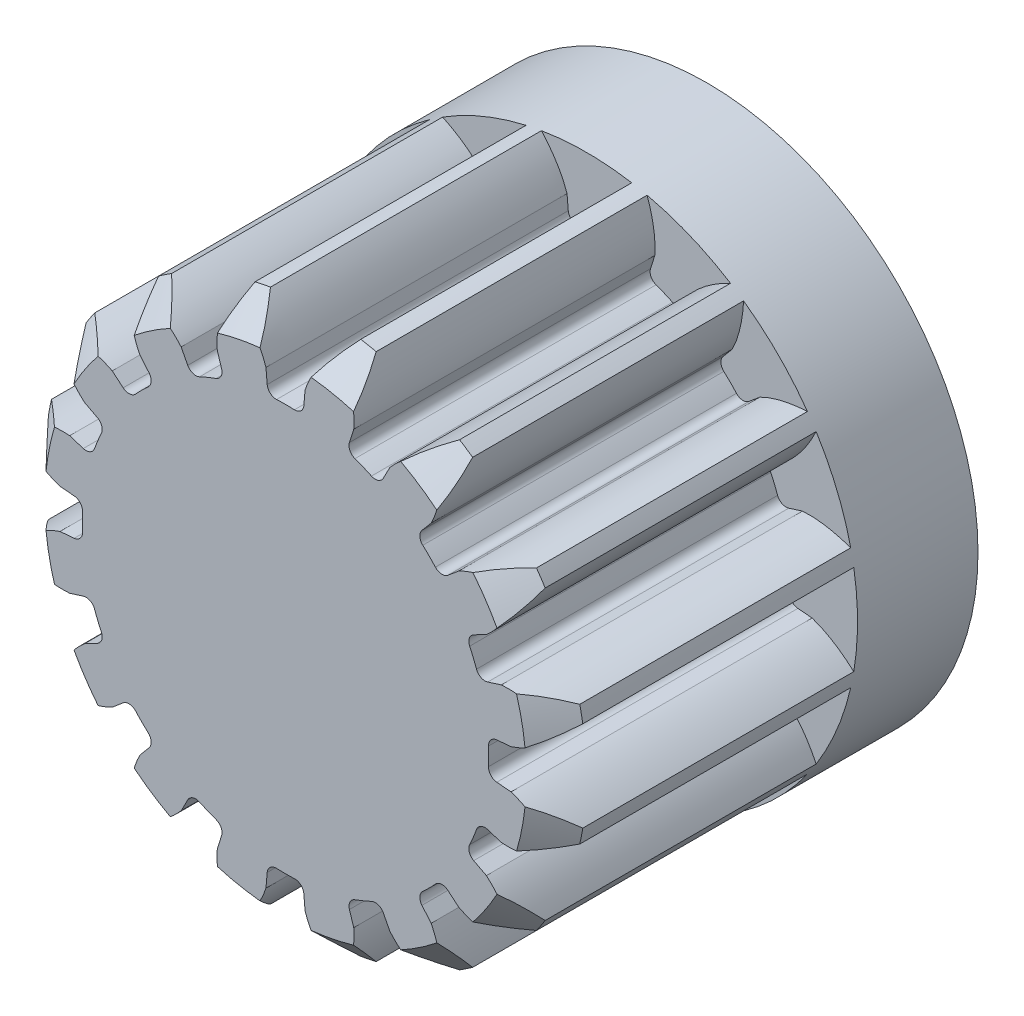
SolidWorks part; units mm, degrees
ref_plane "前视基准面" through (0, 0, 0) normal (0, 0, 1) x (1, 0, 0)
ref_plane "上视基准面" through (0, 0, 0) normal (0, 1, 0) x (1, 0, 0)
ref_plane "右视基准面" through (0, 0, 0) normal (1, 0, 0) x (0, 0, -1)
sketch "直齿轮" plane through (0, 0, 0) normal (0, 0, 1) x (1, 0, 0)
  line L0 (0, 9) -> (0, -9) construction
  line L1 (0, 0) -> (-0.6495, 7.4894)
  line L2 (0, 0) -> (0.6495, 7.4894)
  circle A0 centre (0, 0) radius 9
  arc A1 (0.7841, 7.9615) -> (-0.7841, 7.9615) centre (0, 0) ccw
  circle A2 centre (0, 0) radius 6.75
  circle A3 centre (0, 0) radius 7.5175
  spline S0 degree 4 poles (0.0781, 7.329) (0.077, 7.3576) (0.0721, 7.4145) (0.0444, 7.5728) (-0.044, 7.8662) (-0.2393, 8.2942) (-0.5932, 8.8351) (-1.1432, 9.4579) (-1.8896, 10.0833) (-2.7997, 10.6455) (-3.8544, 11.1099) (-4.9579, 11.4403) (-6.0912, 11.644) (-7.296, 11.7321) (-8.7914, 11.6852) (-10.5554, 11.401) (-12.5357, 10.7749) (-14.6014, 9.7479) (-16.4971, 8.4351) (-18.1977, 6.8792) (-19.6854, 5.1194) (-20.7905, 3.4336) (-21.5928, 1.9052) (-22.1636, 0.5865) (-22.5615, -0.4928) (-22.9004, -1.5905) (-23.1806, -2.7072) (-23.4023, -3.8323) (-23.5456, -4.8331) (-23.6323, -5.6826) (-23.6776, -6.3617) (-23.699, -6.8068) (-23.7118, -7.3077) (-23.715, -7.634) (-23.7125, -8.1596) (-23.6992, -8.5689) (-23.6779, -9.0652) (-23.6471, -9.5073) (-23.6078, -9.983) (-23.5595, -10.4339) (-23.517, -10.787) (-23.4856, -11.012) (-23.4693, -11.1287) knots 0 0 0 0 0 0.002802 0.005604 0.015718 0.02996 0.048734 0.068727 0.096889 0.125051 0.153212 0.181374 0.209535 0.237696 0.271429 0.327752 0.384075 0.440398 0.496721 0.553044 0.609367 0.66569 0.693852 0.722013 0.750174 0.778336 0.806497 0.834659 0.86282 0.876901 0.890982 0.900036 0.909091 0.920455 0.931818 0.943182 0.954545 0.965909 0.977273 0.988636 1 1 1 1 1 construction
  spline S1 degree 4 poles (-0.6495, 7.4894) (-0.6695, 7.5517) (-0.7404, 7.7468) (-0.9116, 8.1035) (-1.2415, 8.6) (-1.7832, 9.2048) (-2.5168, 9.8107) (-3.41, 10.3537) (-4.4437, 10.8002) (-5.5242, 11.1155) (-6.6329, 11.3066) (-7.8108, 11.3844) (-9.2716, 11.3283) (-10.9933, 11.0384) (-12.9239, 10.4129) (-14.9352, 9.3952) (-16.7784, 8.0994) (-18.4293, 6.5673) (-19.8708, 4.8376) (-20.9389, 3.1827) (-21.7123, 1.6839) (-22.2609, 0.3914) (-22.6422, -0.6659) (-22.9658, -1.7408) (-23.2319, -2.8339) (-23.4407, -3.9348) (-23.5738, -4.9136) (-23.6527, -5.7442) (-23.6922, -6.408) (-23.7101, -6.8431) (-23.7191, -7.3326) (-23.72, -7.6515) (-23.7154, -8.0397) (-23.7087, -8.2696) (-23.7044, -8.3867) (-23.7041, -8.3947) knots 0.009155 0.009155 0.009155 0.009155 0.009155 0.015718 0.02996 0.048734 0.068727 0.096889 0.125051 0.153212 0.181374 0.209535 0.237696 0.271429 0.327752 0.384075 0.440398 0.496721 0.553044 0.609367 0.66569 0.693852 0.722013 0.750174 0.778336 0.806497 0.834659 0.86282 0.876901 0.890982 0.900036 0.909091 0.920455 0.931818 0.932653 0.932653 0.932653 0.932653 0.932653
  spline S2 degree 4 poles (-0.0781, 7.329) (-0.077, 7.3576) (-0.0721, 7.4145) (-0.0444, 7.5728) (0.044, 7.8662) (0.2393, 8.2942) (0.5932, 8.8351) (1.1432, 9.4579) (1.8896, 10.0833) (2.7997, 10.6455) (3.8544, 11.1099) (4.9579, 11.4403) (6.0912, 11.644) (7.296, 11.7321) (8.7914, 11.6852) (10.5554, 11.401) (12.5357, 10.7749) (14.6014, 9.7479) (16.4971, 8.4351) (18.1977, 6.8792) (19.6854, 5.1194) (20.7905, 3.4336) (21.5928, 1.9052) (22.1636, 0.5865) (22.5615, -0.4928) (22.9004, -1.5905) (23.1806, -2.7072) (23.4023, -3.8323) (23.5456, -4.8331) (23.6323, -5.6826) (23.6776, -6.3617) (23.699, -6.8068) (23.7118, -7.3077) (23.715, -7.634) (23.7125, -8.1596) (23.6992, -8.5689) (23.6779, -9.0652) (23.6471, -9.5073) (23.6078, -9.983) (23.5595, -10.4339) (23.517, -10.787) (23.4856, -11.012) (23.4693, -11.1287) knots 0 0 0 0 0 0.002802 0.005604 0.015718 0.02996 0.048734 0.068727 0.096889 0.125051 0.153212 0.181374 0.209535 0.237696 0.271429 0.327752 0.384075 0.440398 0.496721 0.553044 0.609367 0.66569 0.693852 0.722013 0.750174 0.778336 0.806497 0.834659 0.86282 0.876901 0.890982 0.900036 0.909091 0.920455 0.931818 0.943182 0.954545 0.965909 0.977273 0.988636 1 1 1 1 1 construction
  spline S3 degree 4 poles (0.6495, 7.4894) (0.6695, 7.5517) (0.7404, 7.7468) (0.9116, 8.1035) (1.2415, 8.6) (1.7832, 9.2048) (2.5168, 9.8107) (3.41, 10.3537) (4.4437, 10.8002) (5.5242, 11.1155) (6.6329, 11.3066) (7.8108, 11.3844) (9.2716, 11.3283) (10.9933, 11.0384) (12.9239, 10.4129) (14.9352, 9.3952) (16.7784, 8.0994) (18.4293, 6.5673) (19.8708, 4.8376) (20.9389, 3.1827) (21.7123, 1.6839) (22.2609, 0.3914) (22.6422, -0.6659) (22.9658, -1.7408) (23.2319, -2.8339) (23.4407, -3.9348) (23.5738, -4.9136) (23.6527, -5.7442) (23.6922, -6.408) (23.7101, -6.8431) (23.7191, -7.3326) (23.72, -7.6515) (23.7154, -8.0397) (23.7087, -8.2696) (23.7044, -8.3867) (23.7041, -8.3947) knots 0.009155 0.009155 0.009155 0.009155 0.009155 0.015718 0.02996 0.048734 0.068727 0.096889 0.125051 0.153212 0.181374 0.209535 0.237696 0.271429 0.327752 0.384075 0.440398 0.496721 0.553044 0.609367 0.66569 0.693852 0.722013 0.750174 0.778336 0.806497 0.834659 0.86282 0.876901 0.890982 0.900036 0.909091 0.920455 0.931818 0.932653 0.932653 0.932653 0.932653 0.932653
  dimension "齿顶圆" = 18
  dimension "分度圆" = 16
  dimension "齿根圆" = 13.5
  dimension "基圆直径" = 15.0351
  dimension "D1" = 1.5708
extrude "齿轮毛坯" add sketch "直齿轮" along normal mid plane 11 contours A0
chamfer "轮齿倒角" distance 1 angle 45 2 edges at (9, 0, -5.5) (9, 0, 5.5)
sketch "草图2" plane through (0, 0, 0) normal (0, 0, 1) x (1, 0, 0)
  line L0 (0, 0) -> (-0.6495, 7.4894) construction
  line L1 (0, 0) -> (0.6495, 7.4894) construction
  line L2 (0, 0) -> (-0.6495, 7.4894)
  line L3 (0, 0) -> (0.6495, 7.4894)
  circle A0 centre (0, 0) radius 9 construction
  circle A1 centre (0, 0) radius 9
  circle A2 centre (0, 0) radius 6.75 construction
  circle A3 centre (0, 0) radius 6.75
  spline S0 degree 4 poles (-1000.5185, -8.0268) (-22.1181, -4.5363) (-0.6894, 1.4333) (0.6229, 5.7939) (-1.2415, 8.6) (-1.7832, 9.2048) (-2.5168, 9.8107) (-3.41, 10.3537) (-4.4437, 10.8002) (-5.5242, 11.1155) (-6.6329, 11.3066) (-7.8108, 11.3844) (-9.2716, 11.3283) (-10.9933, 11.0384) (-12.9239, 10.4129) (-14.9352, 9.3952) (-16.7784, 8.0994) (-18.4293, 6.5673) (-19.8708, 4.8376) (-20.9389, 3.1827) (-21.7123, 1.6839) (-22.2609, 0.3914) (-22.6422, -0.6659) (-22.9658, -1.7408) (-23.2319, -2.8339) (-23.4407, -3.9348) (-23.5738, -4.9136) (-23.6527, -5.7442) (-23.6922, -6.408) (-23.7101, -6.8431) (-23.7191, -7.3326) (-23.72, -7.6515) (-23.6888, -10.2883) (-23.3833, -8.7061) (-23.0999, -55.7183) (-17.6667, 991.4298) knots -0.26796 -0.26796 -0.26796 -0.26796 -0.26796 0.015718 0.02996 0.048734 0.068727 0.096889 0.125051 0.153212 0.181374 0.209535 0.237696 0.271429 0.327752 0.384075 0.440398 0.496721 0.553044 0.609367 0.66569 0.693852 0.722013 0.750174 0.778336 0.806497 0.834659 0.86282 0.876901 0.890982 0.900036 0.909091 0.920455 0.931818 1.121583 1.121583 1.121583 1.121583 1.121583 only from (-0.6495, 7.4894) to (-23.7041, -8.3947) construction
  spline S1 degree 4 poles (-0.6495, 7.4894) (-0.6695, 7.5517) (-0.7404, 7.7468) (-0.9116, 8.1035) (-1.2415, 8.6) (-1.7832, 9.2048) (-2.5168, 9.8107) (-3.41, 10.3537) (-4.4437, 10.8002) (-5.5242, 11.1155) (-6.6329, 11.3066) (-7.8108, 11.3844) (-9.2716, 11.3283) (-10.9933, 11.0384) (-12.9239, 10.4129) (-14.9352, 9.3952) (-16.7784, 8.0994) (-18.4293, 6.5673) (-19.8708, 4.8376) (-20.9389, 3.1827) (-21.7123, 1.6839) (-22.2609, 0.3914) (-22.6422, -0.6659) (-22.9658, -1.7408) (-23.2319, -2.8339) (-23.4407, -3.9348) (-23.5738, -4.9136) (-23.6527, -5.7442) (-23.6922, -6.408) (-23.7101, -6.8431) (-23.7191, -7.3326) (-23.72, -7.6515) (-23.7154, -8.0397) (-23.7087, -8.2696) (-23.7044, -8.3867) (-23.7041, -8.3947) knots 0.009155 0.009155 0.009155 0.009155 0.009155 0.015718 0.02996 0.048734 0.068727 0.096889 0.125051 0.153212 0.181374 0.209535 0.237696 0.271429 0.327752 0.384075 0.440398 0.496721 0.553044 0.609367 0.66569 0.693852 0.722013 0.750174 0.778336 0.806497 0.834659 0.86282 0.876901 0.890982 0.900036 0.909091 0.920455 0.931818 0.932653 0.932653 0.932653 0.932653 0.932653
  spline S2 degree 4 poles (1000.5185, -8.0268) (22.1181, -4.5363) (0.6894, 1.4333) (-0.6229, 5.7939) (1.2415, 8.6) (1.7832, 9.2048) (2.5168, 9.8107) (3.41, 10.3537) (4.4437, 10.8002) (5.5242, 11.1155) (6.6329, 11.3066) (7.8108, 11.3844) (9.2716, 11.3283) (10.9933, 11.0384) (12.9239, 10.4129) (14.9352, 9.3952) (16.7784, 8.0994) (18.4293, 6.5673) (19.8708, 4.8376) (20.9389, 3.1827) (21.7123, 1.6839) (22.2609, 0.3914) (22.6422, -0.6659) (22.9658, -1.7408) (23.2319, -2.8339) (23.4407, -3.9348) (23.5738, -4.9136) (23.6527, -5.7442) (23.6922, -6.408) (23.7101, -6.8431) (23.7191, -7.3326) (23.72, -7.6515) (23.6888, -10.2883) (23.3833, -8.7061) (23.0999, -55.7183) (17.6667, 991.4298) knots -0.26796 -0.26796 -0.26796 -0.26796 -0.26796 0.015718 0.02996 0.048734 0.068727 0.096889 0.125051 0.153212 0.181374 0.209535 0.237696 0.271429 0.327752 0.384075 0.440398 0.496721 0.553044 0.609367 0.66569 0.693852 0.722013 0.750174 0.778336 0.806497 0.834659 0.86282 0.876901 0.890982 0.900036 0.909091 0.920455 0.931818 1.121583 1.121583 1.121583 1.121583 1.121583 only from (0.6495, 7.4894) to (23.7041, -8.3947) construction
  spline S3 degree 4 poles (0.6495, 7.4894) (0.6695, 7.5517) (0.7404, 7.7468) (0.9116, 8.1035) (1.2415, 8.6) (1.7832, 9.2048) (2.5168, 9.8107) (3.41, 10.3537) (4.4437, 10.8002) (5.5242, 11.1155) (6.6329, 11.3066) (7.8108, 11.3844) (9.2716, 11.3283) (10.9933, 11.0384) (12.9239, 10.4129) (14.9352, 9.3952) (16.7784, 8.0994) (18.4293, 6.5673) (19.8708, 4.8376) (20.9389, 3.1827) (21.7123, 1.6839) (22.2609, 0.3914) (22.6422, -0.6659) (22.9658, -1.7408) (23.2319, -2.8339) (23.4407, -3.9348) (23.5738, -4.9136) (23.6527, -5.7442) (23.6922, -6.408) (23.7101, -6.8431) (23.7191, -7.3326) (23.72, -7.6515) (23.7154, -8.0397) (23.7087, -8.2696) (23.7044, -8.3867) (23.7041, -8.3947) knots 0.009155 0.009155 0.009155 0.009155 0.009155 0.015718 0.02996 0.048734 0.068727 0.096889 0.125051 0.153212 0.181374 0.209535 0.237696 0.271429 0.327752 0.384075 0.440398 0.496721 0.553044 0.609367 0.66569 0.693852 0.722013 0.750174 0.778336 0.806497 0.834659 0.86282 0.876901 0.890982 0.900036 0.909091 0.920455 0.931818 0.932653 0.932653 0.932653 0.932653 0.932653
extrude "插齿" cut sketch "草图2" against normal mid plane 11 contours A3 S3 A1 S1 region at (0, 8.051, 0)
fillet "圆角1" radius 0.3 2 edges at (0.5832, 6.7248, 0) (-0.5832, 6.7248, 0)
pattern_circular "圆周阵列1" count 16 over 360 about axis through (0, 0, 5.5) along (0, 0, -1) of "插齿", "圆角1"
fillet "圆角2" [suppressed] radius 0.3
pattern_circular "圆周阵列2" [suppressed] count 16 over 360 of bodies 102
pattern_circular "圆周阵列3" [suppressed] count 16 over 360 of bodies 102
sketch "分度圆" plane through (0, 0, 0) normal (0, 0, 1) x (1, 0, 0)
  circle A0 centre (0, 0) radius 8 construction
sketch "草图3" plane through (0, 0, -5.5) normal (0, 0, -1) x (-1, 0, 0)
  circle A0 centre (0, 0) radius 9
  dimension "D1" = 18
extrude "凸台-拉伸1" add sketch "草图3" along normal blind 4 from offset 1 offset against normal yes
sketch "草图4" plane through (0, 0, 5.5) normal (0, 0, 1) x (1, 0, 0)
  line L0 (-1.0312, 1.2667) -> (1.0312, 1.2667)
  circle A0 centre (0, 0) radius 1.6333
  dimension "D1" = 3.2667
  dimension "D2" = 1.2667
extrude "切除-拉伸1" cut sketch "草图4" against normal through all contours L0 A0 region at (0, -0.0929, 5.5)
scale "缩放比例1" scale about centroid uniform scaling yes scale factor 1.5
sketch "草图5" plane through (0, 0, 9.2318) normal (0, 0, 1) x (1, 0, 0)
  line L0 (-1.5468, 1.8982) -> (1.5468, 1.8982) construction
  line L1 (-1.5468, 1.8982) -> (1.5468, 1.8982)
  arc A0 (-1.5468, 1.8982) -> (1.5468, 1.8982) centre (0, -0.0018) ccw construction
  arc A1 (-1.5468, 1.8982) -> (1.5468, 1.8982) centre (0, -0.0018) ccw
extrude "凸台-拉伸2" add sketch "草图5" against normal blind 3
sketch "草图7" plane through (0, 0, -11.7682) normal (0, 0, -1) x (-1, 0, 0)
  line L0 (-1.65, 2.2) -> (1.65, 2.2)
  circle A0 centre (0, 0) radius 2.75
  arc M4 (1.5468, 1.8982) -> (-1.5468, 1.8982) centre (0, -0.0018) cw
  line M5 (-1.5468, 1.8982) -> (1.5468, 1.8982)
  dimension "D1" = 5.5
  dimension "D2" = 2.2
extrude "切除-拉伸2" cut sketch "草图7" against normal up to next contours L0 A0 M5 M4 | M4 M5 region at (0, 2.126, -11.7682) region at (0, -0.1412, -11.7682)
sketch "草图8" plane through (0, 0, 9.2318) normal (0, 0, 1) x (1, 0, 0)
  line L0 (1.65, 2.2) -> (-1.65, 2.2) construction
  line L1 (1.65, 2.2) -> (-1.65, 2.2)
  arc A0 (-1.65, 2.2) -> (1.65, 2.2) centre (0, 0) ccw construction
  arc A1 (-1.65, 2.2) -> (1.65, 2.2) centre (0, 0) ccw
extrude "凸台-拉伸3" add sketch "草图8" against normal blind 3
equation "\"m\"= 1'模数"
equation "\"z\"= 16'齿数"
equation "\"a\"= 20'压力角（常见为20°）"
equation "\"B\"= 11'齿宽"
equation "\"C1\"= 1'轮齿倒角（若设为0，则无倒角）"
equation "\"R\"= 0.3'齿根圆角（若设为0，则无圆角）"
equation "\"x\"= 0'变位系数"
equation "\"ha\"= 1'齿顶高系数"
equation "\"c\"= 0.25'顶隙系数"
equation "\"分度圆@直齿轮\"=\"m\" * \"z\""
equation "\"齿顶圆@直齿轮\" = \"m\" * ( \"z\" + 2 * ( \"ha\" + \"x\" ) )"
equation "\"齿根圆@直齿轮\" = \"m\" * ( \"z\" - 2 * ( \"ha\" - \"x\" + \"c\" ) )"
equation "\"基圆直径@直齿轮\"= \"m\" * \"z\" * cos ( \"a\" )"
equation "\"D1@直齿轮\"= \"m\" * ( pi / 2 ) - 2 * \"m\" * tan ( \"a\" ) * \"x\"'作者：机械菌-"
equation "\"圆周阵列3\"= IIF ( \"R\">0 , \"suppressed\" , \"unsuppressed\" )"
equation "\"圆角1\"=IIF ( \"R\">0 ,IIF ( \"m\" * ( \"z\" - 2 * ( \"ha\" - \"x\" + \"c\" ) ) < \"m\" * \"z\" * cos ( \"a\" ) , \"unsuppressed\" , \"suppressed\" ) , \"suppressed\" )"
equation "\"圆周阵列1\"=IIF ( \"R\">0 , IIF ( \"m\" * ( \"z\" - 2 * ( \"ha\" - \"x\" + \"c\" ) ) < \"m\" * \"z\" * cos ( \"a\" ) , \"unsuppressed\" , \"suppressed\" ), \"suppressed\" )"
equation "\"圆角2\"=IIF ( \"R\">0 ,IIF ( \"m\" * ( \"z\" - 2 * ( \"ha\" - \"x\" + \"c\" ) ) > \"m\" * \"z\" * cos ( \"a\" ) , \"unsuppressed\" , \"suppressed\" ) , \"suppressed\" )"
equation "\"圆周阵列2\"=IIF ( \"R\">0 , IIF ( \"m\" * ( \"z\" - 2 * ( \"ha\" - \"x\" + \"c\" ) ) > \"m\" * \"z\" * cos ( \"a\" ) , \"unsuppressed\" , \"suppressed\" ), \"suppressed\" )"
equation "\"轮齿倒角\"= IIF ( \"C1\" > 0 , \"unsuppressed\" , \"suppressed\" )"
